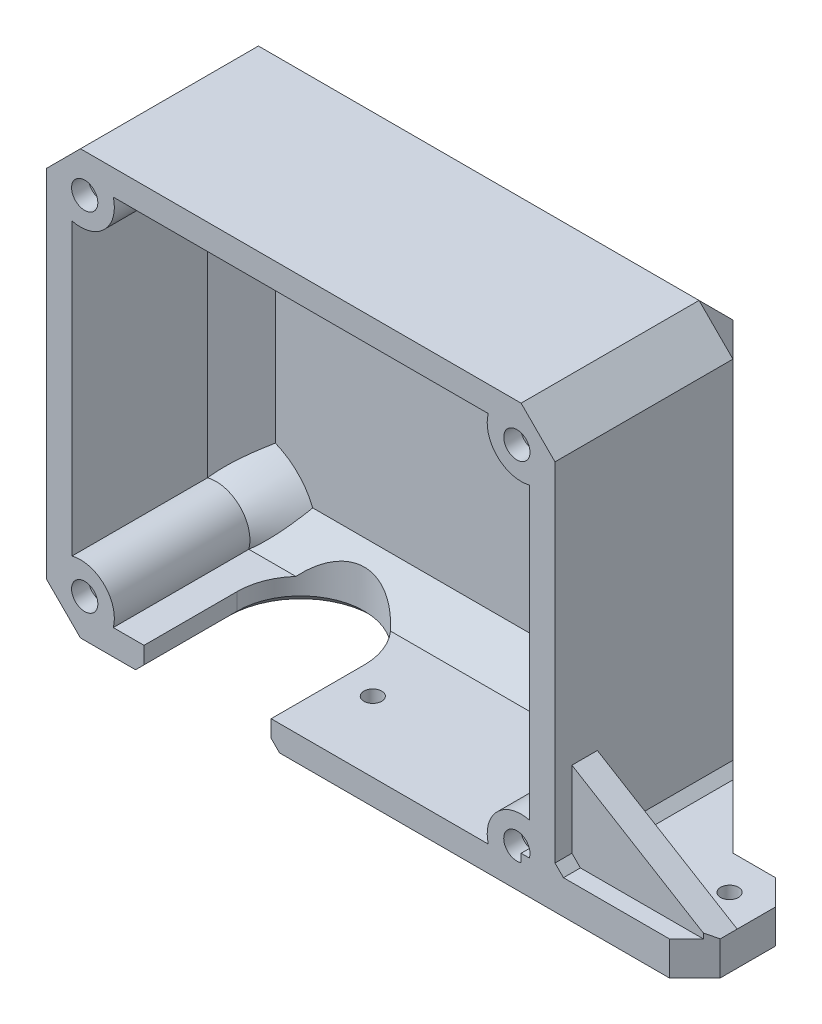
SolidWorks part; units mm, degrees
ref_plane "Front Plane" through (0, 0, 0) normal (0, 0, 1) x (1, 0, 0)
ref_plane "Top Plane" through (0, 0, 0) normal (0, 1, 0) x (1, 0, 0)
ref_plane "Right Plane" through (0, 0, 0) normal (1, 0, 0) x (0, 0, -1)
sketch "Sketch1" plane through (0, 0, 0) normal (0, 0, 1) x (1, 0, 0)
  line L0 (0, 0) -> (0, 50)
  line L1 (0, 50) -> (60, 50)
  line L2 (60, 50) -> (60, 0)
  line L3 (60, 0) -> (0, 0)
extrude "Boss-Extrude1" add sketch "Sketch1" along normal blind 5
sketch "Sketch2" plane through (0, 0, 5) normal (0, 0, 1) x (1, 0, 0)
  line L0 (60, 50) -> (0, 50) construction
  line L1 (0, 50) -> (0, 0) construction
  line L2 (60, 0) -> (60, 50) construction
  line L3 (3, 25) -> (57, 25) construction
  line L8 (57, 3) -> (57, 47)
  line L9 (3, 3) -> (57, 3)
  line L10 (3, 47) -> (3, 3)
  line L11 (57, 47) -> (3, 47)
  line L12 (57, 3) -> (57, 47)
  line L13 (3, 3) -> (57, 3)
  line L14 (3, 47) -> (3, 3)
  line L15 (57, 47) -> (3, 47)
  circle A0 centre (4, 46) radius 4
  circle A1 centre (56, 46) radius 4
  circle A2 centre (56, 4) radius 4
  circle A3 centre (4, 4) radius 4
  line M5 (0, 0) -> (60, 0)
  line M6 (60, 0) -> (60, 50)
  line M7 (60, 50) -> (0, 50)
  line M8 (0, 50) -> (0, 0)
  dimension "D2" = 8
  dimension "D3" = 8
  dimension "D4" = 4
  dimension "D5" = 4
  dimension "D6" = 4
  dimension "D7" = 4
  dimension "D1" = 3
extrude "Boss-Extrude2" add sketch "Sketch2" along normal blind 20 contours A1 A0 L15 M7 | A0 M7 M8 | L15 A0 L14 | A3 L14 A0 M8 | L14 A0 L15 | A3 L13 L14 | A3 M5 M8 | L13 A3 A2 M5 | A3 L14 L13 | A2 L12 L13 | A2 M6 M5 | A2 L13 L12 | L12 A2 A1 M6 | A1 M6 M7 | A1 L15 L12 | L15 A1 L12 region at (54.7572, 5.2428, 5) region at (57.1113, 5.4365, 5) region at (58.5396, 25, 5) region at (30, 1.4689, 5) region at (54.7572, 44.7572, 5) region at (57.1113, 44.5635, 5) region at (59.1065, 0.8935, 5) region at (6.3813, 0.9257, 5) region at (5.2428, 5.2428, 5) region at (30, 48.5311, 5) region at (59.1065, 49.1065, 5) region at (0.8935, 0.8935, 5) region at (5.2428, 44.7572, 5) region at (5.4365, 47.1113, 5) region at (1.4604, 25, 5) region at (0.8935, 49.1065, 5)
chamfer "Chamfer1" distance 4 angle 45 8 edges at (30, 3, 5) (6.8284, 43.1716, 5) (3, 25, 5) (30, 47, 5) (53.1716, 43.1716, 5) (57, 25, 5) (53.1716, 6.8284, 5) (6.8284, 6.8284, 5)
chamfer "Chamfer2" distance 4 angle 45 8 edges at (60, 25, 0) (60, 50, 12.5) (30, 50, 0) (0, 50, 12.5) (0, 25, 0) (60, 0, 12.5) (30, 0, 0) (0, 0, 12.5)
sketch "Sketch3" plane through (0, 0, 0) normal (0, -1, 0) x (1, 0, 0)
  line L0 (4, 25) -> (4, 4) construction
  line L1 (4, 4) -> (56, 4) construction
  line L2 (11.5, 14) -> (11.5, 25)
  line L3 (4, 25) -> (56, 25) construction
  line L4 (26.5, 14) -> (26.5, 25)
  line L5 (26.5, 25) -> (11.5, 25)
  circle A0 centre (19, 14) radius 7.5
  line M3 (56, 25) -> (4, 25)
  dimension "D1" = 15
  dimension "D2" = 15
  dimension "D3" = 10
extrude "Cut-Extrude1" cut sketch "Sketch3" against normal up to next contours A0 L4 L2 M3 | A0 region at (19, 0, 22.171) region at (19, 0, 14)
sketch "Sketch5" plane through (0, 0, 25) normal (0, 0, 1) x (1, 0, 0)
  line L0 (0, 25) -> (60, 25) construction
  line L1 (0, 46) -> (0, 4) construction
  line L2 (60, 4) -> (60, 46) construction
  line L3 (56, 50) -> (4, 50) construction
  circle A0 centre (4.5, 45.5) radius 1.55
  circle A1 centre (55.5, 45.5) radius 1.55
  circle A2 centre (55.5, 4.5) radius 1.55
  circle A3 centre (4.5, 4.5) radius 1.55
  dimension "D1" = 3.1
  dimension "D2" = 3.1
  dimension "D3" = 4.5
  dimension "D4" = 4.5
  dimension "D5" = 4.5
  dimension "D6" = 4.5
extrude "Cut-Extrude2" cut sketch "Sketch5" against normal blind 2
chamfer "Chamfer3" distance 1 angle 45 3 edges at (26.5, 0, 19.5) (11.5, 0, 19.5) (19, 0, 6.5)
sketch "Sketch6" plane through (0, 0, 0) normal (0, -1, 0) x (1, 0, 0)
  line L0 (60, 25) -> (60, 4) construction
  line L1 (60, 4) -> (56, 0) construction
  line L2 (60, 25) -> (60, 4)
  line L3 (60, 4) -> (56, 0)
  line L4 (60, 4) -> (68.4853, 12.4853)
  line L5 (68.4853, 12.4853) -> (76.5, 12.4853)
  line L6 (66.5, 11) -> (66.5, 54) construction
  line L10 (76.5, 12.4853) -> (76.5, 25)
  line L11 (76.5, 25) -> (60, 25)
  line L12 (56, 0) -> (56, 25)
  line L13 (56, 25) -> (60, 25)
  line M8 (56, 4) -> (56, 25)
  dimension "D1" = 12
  dimension "D2" = 10
extrude "Boss-Extrude3" add sketch "Sketch6" against normal blind 4 contours L10 L11 L2 L4 L5 | L11 L2 | L13 L2 M8 | L12 L3 L2 M8 region at (67.4451, 0, 17.3938) region at (57.942, 0, 13.471)
sketch "Sketch7" plane through (56, 0, 0) normal (-1, 0, 0) x (0, 0, 1)
  line L3 (4, 0) -> (0, 4)
  line L4 (0, 4) -> (0, 0)
  line L5 (0, 0) -> (4, 0)
  line L6 (4, 0) -> (0, 4)
  line L7 (0, 4) -> (0, 0)
  line L8 (0, 0) -> (4, 0)
  dimension "D1" = 0
extrude "Cut-Extrude3" cut sketch "Sketch7" against normal up to next
ref_plane "Plane1" through (0, 0, 23) normal (0, 0, 1) x (1, 0, 0)
sketch "Sketch10" plane through (0, 0, 0) normal (0, -1, 0) x (1, 0, 0)
  circle A0 centre (72.3, 16.7) radius 1.05 construction
  circle A1 centre (30.2, 16.7) radius 1.05 construction
  circle A2 centre (72.3, 16.7) radius 1.05
  circle A3 centre (30.2, 16.7) radius 1.05
extrude "Cut-Extrude5" cut sketch "Sketch10" against normal up to next
sketch "Sketch11" plane through (0, 0, 23) normal (0, 0, 1) x (1, 0, 0)
  line L0 (76.5, 4) -> (60, 4) construction
  line L1 (60, 4) -> (60, 46) construction
  line L2 (76.5, 4) -> (60, 4)
  line L3 (60, 4) -> (60, 46)
  line L4 (76.5, 4) -> (60, 14)
  line L5 (60, 14) -> (59, 14)
  line L6 (76.5, 4) -> (76.5, 3)
  line L7 (76.5, 3) -> (59, 3)
  line L8 (59, 3) -> (59, 14)
  dimension "D1" = 10
  dimension "D2" = 1
  dimension "D3" = 1
extrude "Boss-Extrude5" add sketch "Sketch11" against normal blind 3 contours L8 L7 L6 L2 L3 L5 | L2 L4 L3 region at (76.2933, 3.5, 23) region at (65.5, 7.3333, 23)
chamfer "Chamfer6" distance 1 angle 45 2 edges at (60, 4, 24) (60, 4, 12)
chamfer "Chamfer7" distance 3 angle 45 2 edges at (76.5, 2, 25) (76.5, 2, 12.4853)
